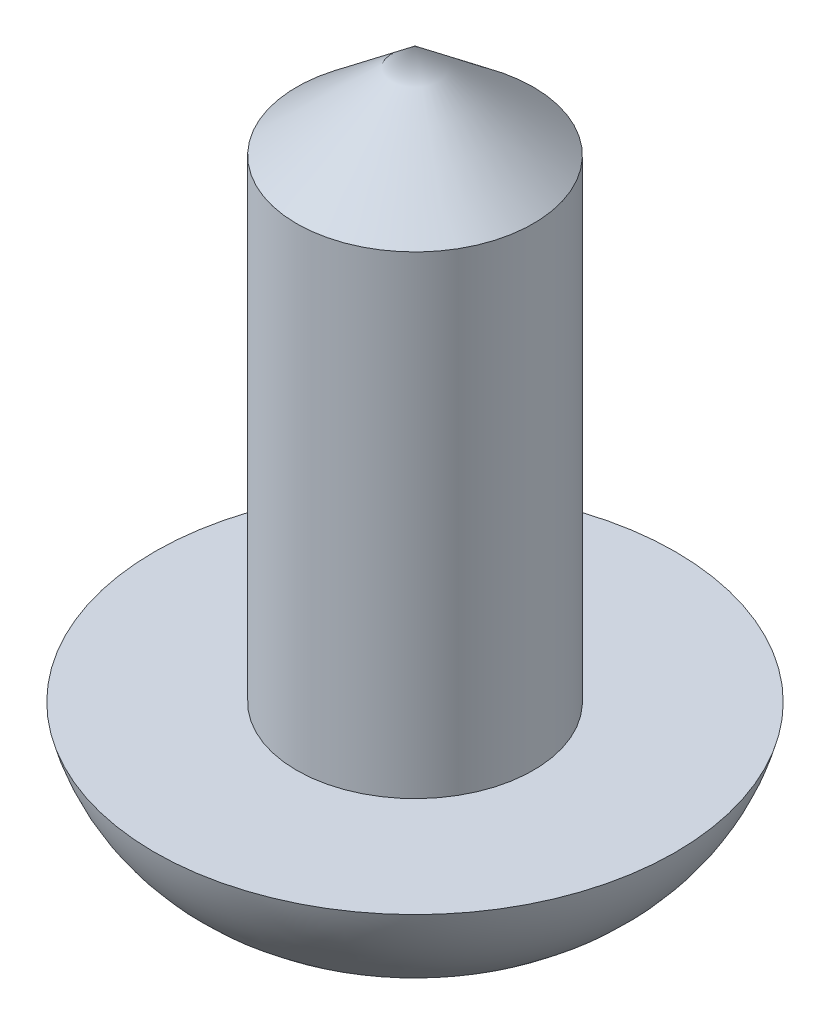
SolidWorks part; units mm, degrees
ref_plane "Front Plane" through (0, 0, 0) normal (0, 0, 1) x (1, 0, 0)
ref_plane "Top Plane" through (0, 0, 0) normal (0, 1, 0) x (1, 0, 0)
ref_plane "Right Plane" through (0, 0, 0) normal (1, 0, 0) x (0, 0, -1)
sketch "Sketch1" plane through (0, 0, 0) normal (0, 1, 0) x (1, 0, 0)
  circle A0 centre (0, 0) radius 1.25
  dimension "D1" = 2.5
extrude "Boss-Extrude1" add sketch "Sketch1" along normal blind 5 contours A0
sketch "Sketch2" plane through (0, 0, 0) normal (0, -1, 0) x (1, 0, 0)
  circle A0 centre (0, 0) radius 2.75
  circle A1 centre (0, 0) radius 1.25 construction
  circle A2 centre (0, 0) radius 1.25 construction
  dimension "D1" = 5.5
extrude "Boss-Extrude2" add sketch "Sketch2" along normal blind 1.5
fillet "Fillet1" radius 2 1 edges at (0, -1.5, -2.75)
sketch "Sketch3" plane through (0, -1.5, 0) normal (0, -1, 0) x (1, 0, 0)
  line L0 (0.375, 0.375) -> (1.5, 0.375)
  line L1 (-0.375, -1.5) -> (0.375, -1.5)
  line L2 (-0.375, -1.5) -> (-0.375, -0.375)
  line L3 (-0.375, 1.5) -> (0.375, 1.5)
  line L4 (0.375, -1.5) -> (0.375, -0.375)
  line L7 (-1.5, -0.375) -> (-0.375, -0.375)
  line L8 (-1.5, -0.375) -> (-1.5, 0.375)
  line L9 (-1.5, 0.375) -> (-0.375, 0.375)
  line L10 (1.5, -0.375) -> (1.5, 0.375)
  line L15 (0.375, 0.375) -> (0.375, 1.5)
  line L16 (0.375, -0.375) -> (1.5, -0.375)
  line L17 (-0.375, 0.375) -> (-0.375, 1.5)
  point P0 (0, 0)
  point P6 (0, 0)
  dimension "D1" = 3
  dimension "D2" = 0.75
extrude "Cut-Extrude1" cut sketch "Sketch3" against normal blind 1 draft 15
sketch "Sketch5" [suppressed] plane through (0, 0, 0) normal (0, 0, 1) x (1, 0, 0)
  line L0 (-2.1, -2) -> (2.1, -2) construction
  line L3 (0, 0) -> (0, 24) construction
  point P6 (0, 11)
  dimension "D1" = 13
  dimension "D2" = 26
sketch "Sketch6" [suppressed] plane through (0, 0, 0) normal (0, 0, 1) x (1, 0, 0)
  line L0 (0, 0) -> (0, 50) construction
  line L1 (4, 50) -> (-4, 50) construction
sketch "Sketch7" [suppressed] plane through (0, 0, 0) normal (1, 0, 0) x (0, 0, -1)
  line L0 (0, 10) -> (0, 50010) construction
  line L1 (1.5875, 25.4) -> (-1.5875, 25.4) construction
  line L2 (-1.5875, 25.4) -> (0, 25.4)
  line L3 (0, 25.4) -> (0, 27.4)
  line L4 (0, 27.4) -> (-1.5875, 25.4)
  point P4 (0, 25.4)
  dimension "D1" = 2
revolve "Revolve1" [suppressed] add sketch "Sketch7" angle 360 about L0
sketch "Sketch8" [suppressed] plane through (0, 0, 0) normal (0, -1, 0) x (1, 0, 0)
  circle A0 centre (0, 0) radius 2.2225
  dimension "D1" = 4.445
extrude "Boss-Extrude3" [suppressed] add sketch "Sketch8" along normal blind 3
sketch "Sketch9" [suppressed] plane through (0, -3, 0) normal (0, -1, 0) x (1, 0, 0)
  circle A0 centre (0, 0) radius 1.2225
  circle A1 centre (0, 0) radius 2.2225 construction
  dimension "D1" = 1
extrude "Cut-Extrude2" [suppressed] cut sketch "Sketch9" against normal offset from surface (2 mm away) 1
sketch "Sketch11" plane through (0, 0, 0) normal (0, 0, 1) x (1, 0, 0)
  line L0 (0, 5) -> (0, 6)
  line L1 (1.25, 5) -> (-1.25, 5) construction
  line L2 (0, 6) -> (-1.25, 5)
  line L3 (-1.25, 5) -> (0, 5)
  line L4 (-1.25, 5) -> (-1.25, 0) construction
  dimension "D1" = 1
revolve "Revolve2" add sketch "Sketch11" angle 360 about L0
